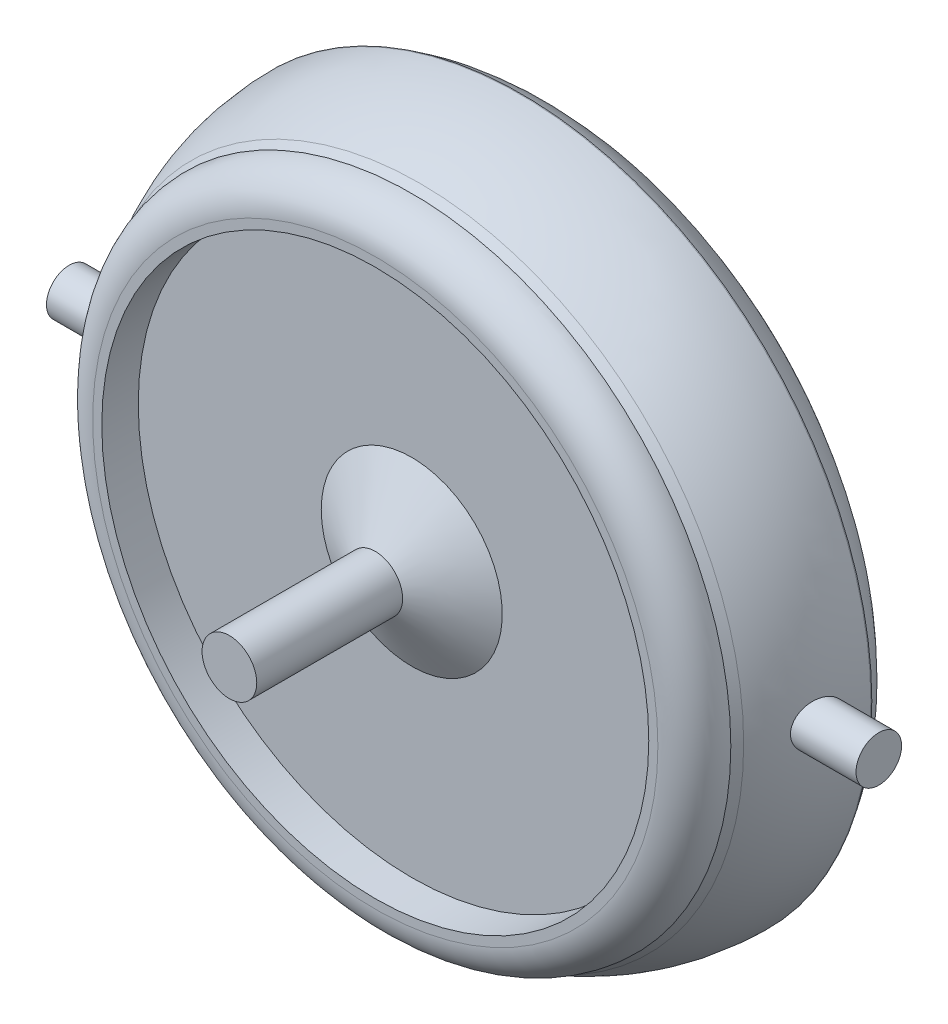
SolidWorks part; units mm, degrees
ref_plane "Front Plane" through (0, 0, 0) normal (0, 0, 1) x (1, 0, 0)
ref_plane "Top Plane" through (0, 0, 0) normal (0, 1, 0) x (1, 0, 0)
ref_plane "Right Plane" through (0, 0, 0) normal (1, 0, 0) x (0, 0, -1)
sketch "Sketch1" plane through (0, 0, 0) normal (0, 0, 1) x (1, 0, 0)
  circle A0 centre (0, 0) radius 15
extrude "Boss-Extrude1" add sketch "Sketch1" along normal blind 80
sketch "Sketch2" plane through (0, 0, 0) normal (0, 0, -1) x (-1, 0, 0)
  circle A0 centre (0, 0) radius 15
extrude "Boss-Extrude2" add sketch "Sketch2" along normal blind 20 draft 60 draft outward yes
sketch "Sketch3" plane through (0, 0, -20) normal (0, 0, -1) x (-1, 0, 0)
  circle A0 centre (0, 0) radius 175
extrude "Boss-Extrude5" add sketch "Sketch3" along normal blind 30 draft 30 draft outward yes
sketch "Sketch6" plane through (0, 0, -20) normal (0, 0, 1) x (1, 0, 0)
  circle A0 centre (0, 0) radius 175
  circle A1 centre (0, 0) radius 150
extrude "Boss-Extrude6" add sketch "Sketch6" along normal blind 20
sketch "Sketch7" plane through (0, 0, -50) normal (0, 0, -1) x (-1, 0, 0)
  circle A0 centre (0, 0) radius 192.3205
  circle A1 centre (0, 0) radius 192.3205 construction
extrude "Boss-Extrude7" add sketch "Sketch7" along normal blind 30
sketch "Sketch9" plane through (0, 0, -80) normal (0, 0, -1) x (-1, 0, 0)
  circle A0 centre (0, 0) radius 192.3205
  circle A1 centre (0, 0) radius 192.3205 construction
extrude "Boss-Extrude8" add sketch "Sketch9" along normal blind 30 draft 30
ref_plane "Plane3" through (-192.3205, 0, 0) normal (-1, 0, 0) x (0, 0, 1)
fillet "Fillet2" radius 60 1 edges at (-175, 0, -110)
fillet "Fillet3" radius 110 1 edges at (-192.3205, 0, -50)
fillet "Fillet4" radius 20 1 edges at (175, 0, 0)
sketch "Sketch10" plane through (-192.3205, 0, 0) normal (-1, 0, 0) x (0, 0, 1)
  line L0 (-79.4744, 192.3205) -> (-79.4744, -192.3205) construction
  circle A0 centre (-54.4744, 0) radius 12.5
  dimension "D1" = 25
extrude "Boss-Extrude9" add sketch "Sketch10" along normal blind 30 and the other way blind 414 contours A0
